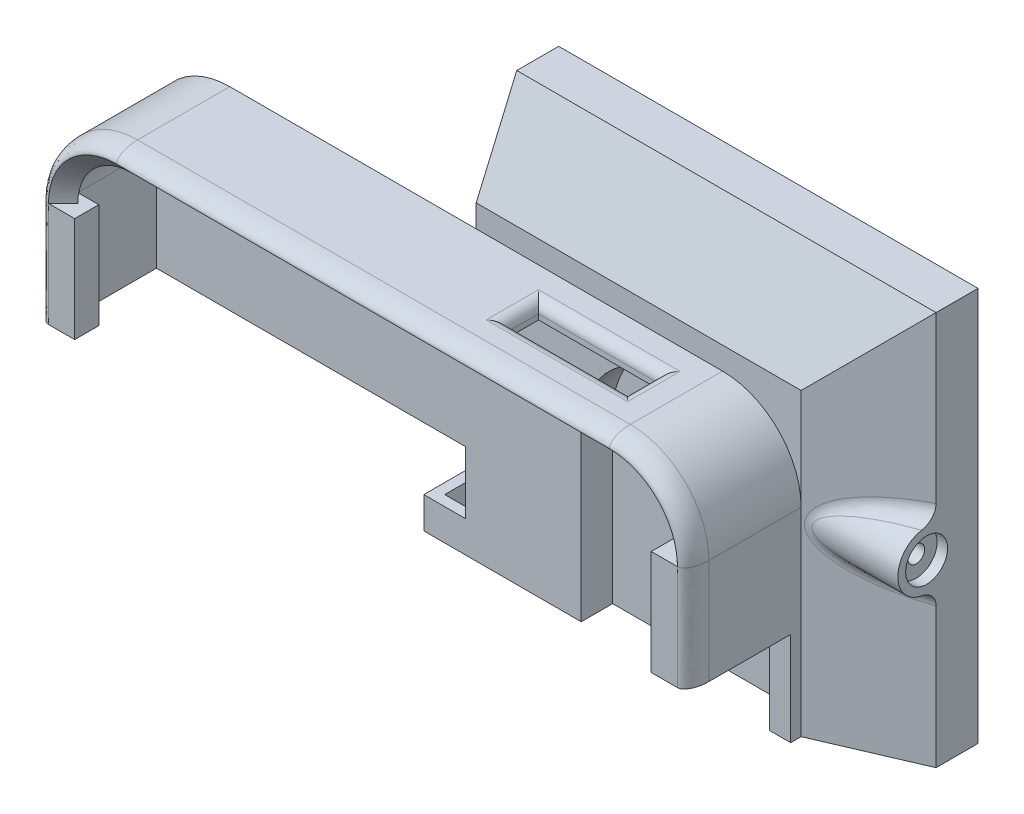
SolidWorks part; units mm, degrees
ref_plane "Front Plane" through (0, 0, 0) normal (0, 0, 1) x (1, 0, 0)
ref_plane "Top Plane" through (0, 0, 0) normal (0, 1, 0) x (1, 0, 0)
ref_plane "Right Plane" through (0, 0, 0) normal (1, 0, 0) x (0, 0, -1)
sketch "Sketch1" plane through (0, 0, 0) normal (0, 0, 1) x (1, 0, 0)
  line L0 (31, 17.5) -> (31, 0)
  line L1 (0, 0) -> (62, 0)
  line L2 (0, 0) -> (0, 10)
  line L3 (7.5, 17.5) -> (54.5, 17.5)
  line L4 (62, 0) -> (62, 10)
  line L5 (7.5, 16) -> (54.5, 16)
  line L9 (1.5, 0) -> (1.5, 10)
  line L12 (60.5, 10) -> (60.5, 0)
  arc A0 (0, 10) -> (7.5, 17.5) centre (7.5, 10) cw
  arc A1 (62, 10) -> (54.5, 17.5) centre (54.5, 10) ccw
  arc A2 (1.5, 10) -> (7.5, 16) centre (7.5, 10) cw
  arc A3 (60.5, 10) -> (54.5, 16) centre (54.5, 10) ccw
  dimension "D5" = 1.5
extrude "Boss-Extrude1" add sketch "Sketch1" along normal blind 10.8 contours L9 A2 L5 L0 L3 A0 L2 L1 | A3 L12 L1 L4 A1 L3 L0 L5 region at (42.75, 17.144, 0) region at (30.644, 16.75, 0)
sketch "Sketch2" plane through (0, 0, 0) normal (0, 0, -1) x (-1, 0, 0)
  line L0 (-1.5, 0) -> (-1.5, 10)
  line L1 (-7.5, 16) -> (-54.5, 16)
  line L2 (-60.5, 0) -> (-60.5, 10)
  line L3 (-60.5, 0) -> (-1.5, 0)
  arc A0 (-1.5, 10) -> (-7.5, 16) centre (-7.5, 10) ccw
  arc A1 (-54.5, 16) -> (-60.5, 10) centre (-54.5, 10) ccw
extrude "Boss-Extrude2" add sketch "Sketch2" against normal blind 1 separate body
combine bodies "Combine1" operation type add bodies to combine 102 101
sketch "Sketch3" plane through (0, 0, 10.8) normal (0, 0, 1) x (1, 0, 0)
  line L0 (0, 0) -> (3.5, 0)
  line L1 (0, 0) -> (0, 10)
  line L2 (0, 0) -> (0, 10) construction
  line L3 (3.5, 0) -> (3.5, 10)
  line L4 (3.5, 10) -> (0, 10)
  line L5 (1.5, 10) -> (1.5, 0)
  line L6 (31, 16) -> (31, -7.5027)
  line L7 (7.5, 16) -> (54.5, 16) construction
  line L8 (60.5, 10) -> (60.5, 0)
  line L9 (62, 0) -> (58.5, 0)
  line L10 (58.5, 10) -> (62, 10)
  line L11 (58.5, 0) -> (58.5, 10)
  line M7 (1.5, 0) -> (1.5, 10)
  line M11 (60.5, 10) -> (60.5, 0)
  dimension "D1" = 3.5
  dimension "D2" = 10
extrude "Boss-Extrude3" add sketch "Sketch3" against normal blind 2.3 contours L3 L4 L0 M7 | L11 L9 L10 M11 region at (2.5, 5, 10.8) region at (59.5, 5, 10.8)
fillet "Fillet1" radius 1 5 edges at (0, 5, 10.8) (62, 5, 10.8) (2.1967, 15.3033, 10.8) (59.8033, 15.3033, 10.8) (31, 17.5, 10.8) second distance 2 first distance on face at (31, 9.4708, 10.8)
sketch "Sketch4" plane through (0, 17.5, 0) normal (0, 1, 0) x (1, 0, 0)
  line L0 (62, -8.8) -> (62, 0) construction
  line L1 (51.5, -6.05) -> (40, -6.05)
  line L2 (51.5, -6.05) -> (51.5, -3.05)
  line L3 (51.5, -3.05) -> (40, -3.05)
  line L4 (40, -6.05) -> (40, -3.05)
  line L5 (7.5, 0) -> (54.5, 0) construction
  dimension "D1" = 10.5
  dimension "D2" = 11.5
  dimension "D3" = 3.05
  dimension "D4" = 3
extrude "Cut-Extrude1" cut sketch "Sketch4" against normal up to next
sketch "Sketch5" plane through (0, 0, 10.8) normal (0, 0, 1) x (1, 0, 0)
  line L1 (7.5, 15) -> (54.5, 15)
  line L2 (7.5, 16) -> (54.5, 16) construction
  line L4 (3.5, 10) -> (1.5, 10) construction
  line L5 (31, 16.5) -> (31, -2.3238) construction
  line L6 (54.5, 16.5) -> (7.5, 16.5) construction
  line L7 (59.5, 10) -> (60.5, 10)
  line L8 (54.5, 16) -> (7.5, 16)
  line L9 (1.5, 10) -> (2.5, 10)
  arc A1 (2.5, 10) -> (7.5, 15) centre (7.5, 10) cw
  arc A2 (59.5, 10) -> (54.5, 15) centre (54.5, 10) ccw
  arc A3 (60.5, 10) -> (54.5, 16) centre (54.5, 10) ccw
  arc A4 (7.5, 16) -> (1.5, 10) centre (7.5, 10) ccw
  dimension "D1" = 1
extrude "Boss-Extrude4" add sketch "Sketch5" against normal blind 2.3
chamfer "Chamfer1" distance 1.5 angle 45 3 edges at (58.0355, 13.5355, 10.8) (31, 15, 10.8) (3.9645, 13.5355, 10.8)
chamfer "Chamfer3" distance 1 angle 45 3 edges at (58.0355, 13.5355, 8.5) (31, 15, 8.5) (3.9645, 13.5355, 8.5)
sketch "Sketch6" plane through (0, 0, 0) normal (0, 0, -1) x (-1, 0, 0)
  line L0 (-59.98, 0) -> (-59.98, 6.7)
  line L1 (-59.98, 0) -> (-42.02, 0)
  line L2 (-42.02, 0) -> (-42.02, 6.7)
  arc A0 (-42.02, 6.7) -> (-59.98, 6.7) centre (-51, 6.7) ccw
extrude "Cut-Extrude2" cut sketch "Sketch6" against normal blind 2
sketch "Sketch9" plane through (0, 0, 0) normal (0, 0, -1) x (-1, 0, 0)
  line L0 (-62, 10) -> (-62, 0)
  line L1 (-62, 0) -> (-59.98, 0)
  line L2 (-59.98, 0) -> (-59.98, 6.7)
  line L3 (-42.02, 6.7) -> (-42.02, 0)
  line L4 (-42.02, 0) -> (-40, 0)
  line L5 (-42.02, 0) -> (0, 0) construction
  line L6 (-40, 0) -> (-40, 10)
  line L8 (-54.5, 17.5) -> (-47.5, 17.5)
  arc A0 (-59.98, 6.7) -> (-42.02, 6.7) centre (-51, 6.7) cw
  arc A1 (-47.5, 17.5) -> (-40, 10) centre (-47.5, 10) cw
  arc A2 (-54.5, 17.5) -> (-62, 10) centre (-54.5, 10) ccw
extrude "Boss-Extrude6" add sketch "Sketch9" along normal blind 2
fillet "Fillet2" radius 1 4 edges at (45.75, 17.5, 3.05) (51.5, 17.5, 4.55) (45.75, 17.5, 6.05) (40, 17.5, 4.55)
sketch "Sketch10" plane through (0, 0, -2) normal (0, 0, -1) x (-1, 0, 0)
  line L0 (-62, 10) -> (-62, 0)
  line L1 (-62, 0) -> (-40, 0)
  line L2 (-40, 0) -> (-40, 10)
  line L3 (-54.5, 17.5) -> (-47.5, 17.5)
  arc A0 (-62, 10) -> (-54.5, 17.5) centre (-54.5, 10) cw
  arc A1 (-40, 10) -> (-47.5, 17.5) centre (-47.5, 10) ccw
extrude "Boss-Extrude7" add sketch "Sketch10" along normal blind 1.87
sketch "Sketch11" plane through (0, 0, -2) normal (0, 0, 1) x (1, 0, 0)
  circle A0 centre (51, 8.65) radius 2.5
  dimension "D1" = 5
extrude "Cut-Extrude3" cut sketch "Sketch11" against normal through all
sketch "Sketch20" plane through (0, 0, -3.87) normal (0, 0, -1) x (-1, 0, 0)
  line L0 (-51, 28.65) -> (-51, -11.35) construction
  line L1 (-71, 28.65) -> (-31, 28.65)
  line L2 (-71, 28.65) -> (-71, -11.35)
  line L3 (-71, -11.35) -> (-31, -11.35)
  line L4 (-31, 28.65) -> (-31, -11.35)
  line L5 (-71, 8.65) -> (-31, 8.65) construction
  line L7 (-68.6, 26.25) -> (-33.4, 26.25)
  line L8 (-68.6, 26.25) -> (-68.6, -8.95)
  line L9 (-68.6, -8.95) -> (-33.4, -8.95)
  line L10 (-33.4, 26.25) -> (-33.4, -8.95)
  circle A0 centre (-51, 8.65) radius 2.5 construction
  dimension "D1" = 40
  dimension "D2" = 40
  dimension "D3" = 0
  dimension "D4" = 0
  dimension "D5" = 35.2
  dimension "D6" = 35.2
  dimension "D7" = 17.6
  dimension "D8" = 17.6
extrude "Boss-Extrude8" add sketch "Sketch20" along normal blind 4 separate body
sketch "Sketch21" plane through (0, 0, 0) normal (0, -1, 0) x (1, 0, 0)
  line L0 (62, -3.87) -> (71, -3.87)
  line L1 (71, -3.87) -> (62, 0)
  line L2 (62, 8.8) -> (62, -3.87) construction
  line L3 (62, 0) -> (62, -3.87)
  dimension "D1" = 9
extrude "Boss-Extrude9" add sketch "Sketch21" along normal up to surface and the other way up to surface up to face at (51, -11.35, -5.87) other way up to face at (51, 28.65, -5.87)
sketch "Sketch28" plane through (0, 0, 0) normal (0, 0, -1) x (-1, 0, 0)
  line L0 (-31, 17.5) -> (-31, 0)
  line L1 (-31, -11.35) -> (-31, 28.65) construction
  line L4 (-40, 10) -> (-40, 0)
  line L5 (-40, 0) -> (0, 0)
  line L6 (0, 0) -> (0, 10)
  line L7 (-7.5, 17.5) -> (-47.5, 17.5)
  line L8 (-40, 10) -> (-40, 0)
  line L9 (-40, 0) -> (0, 0)
  line L10 (0, 0) -> (0, 10)
  line L11 (-7.5, 17.5) -> (-47.5, 17.5)
  arc A2 (-40, 10) -> (-47.5, 17.5) centre (-47.5, 10) ccw
  arc A3 (0, 10) -> (-7.5, 17.5) centre (-7.5, 10) ccw
  arc A4 (-40, 10) -> (-47.5, 17.5) centre (-47.5, 10) ccw
  arc A5 (0, 10) -> (-7.5, 17.5) centre (-7.5, 10) ccw
  arc M7 (-47.5, 17.5) -> (-40, 10) centre (-47.5, 10) cw
  line M8 (-40, 10) -> (-40, 0)
  line M9 (-40, 0) -> (0, 0)
  line M12 (-7.5, 17.5) -> (-47.5, 17.5)
  dimension "D1" = 0
extrude "Boss-Extrude22" add sketch "Sketch28" along normal up to surface (3.87 mm away) contours L0 M12 M7 M8 M9 region at (35.9396, 9.2536, 0) up to face at (53.5, 8.65, -3.87)
sketch "Sketch29" plane through (31, 0, 0) normal (-1, 0, 0) x (0, 0, 1)
  line L0 (-3.87, 28.65) -> (-3.87, 19.65)
  line L1 (-3.87, 17.5) -> (-3.87, 28.65) construction
  line L2 (-3.87, 19.65) -> (0, 19.65)
  line L3 (0, 19.65) -> (-3.87, 28.65)
  line L4 (-3.87, 28.65) -> (-3.8304, 28.713)
  line M6 (-3.87, 17.5) -> (-3.87, 28.65)
  dimension "D1" = 9
extrude "Boss-Extrude23" add sketch "Sketch29" against normal up to surface (40 mm away) contours L2 L3 M6 region at (31, 22.65, -2.58) up to face at (71, 8.65, -5.87)
sketch "Sketch30" plane through (0, 19.65, 0) normal (0, -1, 0) x (1, 0, 0)
  line L3 (62, 0) -> (71, -3.87)
  line L4 (71, -3.87) -> (71, 0)
  line L5 (71, 0) -> (62, 0)
  line L6 (62, 0) -> (71, -3.87)
  line L7 (71, -3.87) -> (71, 0)
  line L8 (71, 0) -> (62, 0)
  dimension "D1" = 0
extrude "Cut-Extrude8" cut sketch "Sketch30" against normal up to next
sketch "Sketch31" plane through (62, 0, 0) normal (-1, 0, 0) x (0, 0, 1)
  line L3 (0, 28.65) -> (-3.87, 28.65)
  line L4 (-3.87, 28.65) -> (0, 19.65)
  line L5 (0, 19.65) -> (0, 28.65)
  line L6 (0, 28.65) -> (-3.87, 28.65)
  line L7 (-3.87, 28.65) -> (0, 19.65)
  line L8 (0, 19.65) -> (0, 28.65)
  dimension "D1" = 0
extrude "Cut-Extrude9" cut sketch "Sketch31" against normal up to next
sketch "Sketch32" plane through (0, 19.65, 0) normal (0, -1, 0) x (1, 0, 0)
  line L5 (62, -3.87) -> (62, 0)
  line L6 (62, 0) -> (31, 0)
  line L7 (31, 0) -> (31, -3.87)
  line L8 (31, -3.87) -> (33.4, -3.87)
  line L9 (33.4, -3.87) -> (62, -3.87)
  line L10 (62, -3.87) -> (62, 0)
  line L11 (62, 0) -> (31, 0)
  line L12 (31, 0) -> (31, -3.87)
  line L13 (31, -3.87) -> (33.4, -3.87)
  line L14 (33.4, -3.87) -> (62, -3.87)
  dimension "D1" = 0
extrude "Boss-Extrude24" add sketch "Sketch32" along normal up to surface (2.15 mm away) up to face at (45.75, 17.5, 4.55)
sketch "Sketch33" plane through (0, 0, -3.87) normal (0, 0, -1) x (-1, 0, 0)
  line L0 (-54.5, 17.5) -> (-62, 17.5)
  line L1 (-62, 17.5) -> (-62, 10)
  arc A0 (-62, 10) -> (-54.5, 17.5) centre (-54.5, 10) cw
extrude "Boss-Extrude25" add sketch "Sketch33" against normal up to surface (3.87 mm away) up to face at (48.1, 18.36, 0)
sketch "Sketch34" plane through (0, 0, 0) normal (0, -1, 0) x (1, 0, 0)
  line L0 (60.5, 1) -> (62, 1)
  line L1 (31, 0) -> (31, 1)
  line L20 (0, 0) -> (31, 0)
  line L21 (31, 0) -> (31, -3.87)
  line L22 (31, -3.87) -> (33.4, -3.87)
  line L23 (33.4, -3.87) -> (62, -3.87)
  line L24 (62, -3.87) -> (62, 0)
  line L25 (62, 0) -> (62, 8.8)
  line L26 (61, 10.8) -> (58.5, 10.8)
  line L27 (58.5, 10.8) -> (58.5, 8.5)
  line L28 (58.5, 8.5) -> (60.5, 8.5)
  line L29 (60.5, 8.5) -> (60.5, 1)
  line L30 (60.5, 1) -> (59.98, 1)
  line L31 (59.98, 1) -> (59.98, -2)
  line L32 (59.98, -2) -> (42.02, -2)
  line L33 (42.02, -2) -> (42.02, 1)
  line L34 (42.02, 1) -> (1.5, 1)
  line L35 (1.5, 1) -> (1.5, 8.5)
  line L36 (1.5, 8.5) -> (3.5, 8.5)
  line L37 (3.5, 8.5) -> (3.5, 10.8)
  line L38 (3.5, 10.8) -> (1, 10.8)
  line L39 (0, 8.8) -> (0, 0)
  line L40 (0, 0) -> (31, 0)
  line L41 (31, 0) -> (31, -3.87)
  line L42 (31, -3.87) -> (33.4, -3.87)
  line L43 (33.4, -3.87) -> (62, -3.87)
  line L44 (62, -3.87) -> (62, 0)
  line L45 (62, 0) -> (62, 8.8)
  line L46 (61, 10.8) -> (58.5, 10.8)
  line L47 (58.5, 10.8) -> (58.5, 8.5)
  line L48 (58.5, 8.5) -> (60.5, 8.5)
  line L49 (60.5, 8.5) -> (60.5, 1)
  line L50 (60.5, 1) -> (59.98, 1)
  line L51 (59.98, 1) -> (59.98, -2)
  line L52 (59.98, -2) -> (42.02, -2)
  line L53 (42.02, -2) -> (42.02, 1)
  line L54 (42.02, 1) -> (1.5, 1)
  line L55 (1.5, 1) -> (1.5, 8.5)
  line L56 (1.5, 8.5) -> (3.5, 8.5)
  line L57 (3.5, 8.5) -> (3.5, 10.8)
  line L58 (3.5, 10.8) -> (1, 10.8)
  line L59 (0, 8.8) -> (0, 0)
  spline S2 degree 2 poles (-2769.6454, -979.1152) (73.4069, -63.5955) (61.954, 9.3993) (61.9047, 9.714) (61.807, 9.9811) (61.6887, 10.3047) (61.5165, 10.5125) (61.4097, 10.6416) (61.2894, 10.7144) (34.7566, 26.7839) (-231.209, -2974.6133) knots -62.059776 -62.059776 -62.059776 0.25 0.25 0.5 0.5 0.75 0.75 0.875 0.875 24.347049 24.347049 24.347049 only from (62, 8.8) to (61, 10.8)
  spline S3 degree 2 poles (259.0787, -2977.8645) (27.3521, 26.7647) (0.7111, 10.7147) (0.592, 10.643) (0.4846, 10.5139) (0.3135, 10.3082) (0.1946, 9.9856) (0.0962, 9.7183) (0.0462, 9.4006) (-11.3863, -63.1555) (2809.0718, -1041.6058) knots -23.400529 -23.400529 -23.400529 0.125 0.125 0.25 0.25 0.5 0.5 0.75 0.75 62.676656 62.676656 62.676656 only from (1, 10.8) to (0, 8.8)
  spline S4 degree 2 poles (62, 8.8) (62, 9.1064) (61.954, 9.3993) (61.9047, 9.714) (61.807, 9.9811) (61.6887, 10.3047) (61.5165, 10.5125) (61.4097, 10.6416) (61.2894, 10.7144) (61.1481, 10.8) (61, 10.8) knots 0 0 0 0.25 0.25 0.5 0.5 0.75 0.75 0.875 0.875 1 1 1
  spline S5 degree 2 poles (1, 10.8) (0.8527, 10.8) (0.7111, 10.7147) (0.592, 10.643) (0.4846, 10.5139) (0.3135, 10.3082) (0.1946, 9.9856) (0.0962, 9.7183) (0.0462, 9.4006) (0, 9.1077) (0, 8.8) knots 0 0 0 0.125 0.125 0.25 0.25 0.5 0.5 0.75 0.75 1 1 1
  line M24 (31, 0) -> (31, -3.87)
  line M25 (31, -3.87) -> (33.4, -3.87)
  line M26 (33.4, -3.87) -> (62, -3.87)
  line M27 (62, -3.87) -> (62, 0)
  line M28 (62, 0) -> (62, 8.8)
  line M34 (60.5, 1) -> (59.98, 1)
  line M35 (59.98, 1) -> (59.98, -2)
  line M36 (59.98, -2) -> (42.02, -2)
  line M37 (42.02, -2) -> (42.02, 1)
  line M38 (42.02, 1) -> (1.5, 1)
  dimension "D1" = 0
extrude "Boss-Extrude26" add sketch "Sketch34" along normal up to surface (11.35 mm away) contours L1 L0 M24 M25 M26 M27 M28 M34 M35 M36 M37 M38 region at (58.1075, 0, -2.3535) region at (39.3369, 0, -1.8217) up to face at (57.25, -11.35, -4.8808)
sketch "Sketch37" plane through (71, 0, 0) normal (1, 0, 0) x (0, 0, -1)
  line L1 (3.87, -11.35) -> (3.87, 28.65) construction
  circle A0 centre (2.97, 8.65) radius 0.8065
  dimension "D2" = 1.613
  dimension "D3" = 0.9
  dimension "D1" = 17.6
extrude "Cut-Extrude13" cut sketch "Sketch37" against normal up to surface (17.5 mm away) up to face at (53.5, 8.65, -2)
sketch "Sketch38" plane through (71, 0, 0) normal (1, 0, 0) x (0, 0, -1)
  line L0 (3.87, 11.2486) -> (3.87, 6.0514)
  line L1 (3.87, -11.35) -> (3.87, 28.65) construction
  circle A0 centre (2.97, 8.65) radius 2.75
  line M3 (3.87, 28.65) -> (3.87, -11.35)
  dimension "D1" = 5.5
extrude "Boss-Extrude27" add sketch "Sketch38" against normal up to surface (9 mm away) contours A0 M3 region at (71, 8.65, -2.2712) up to face at (62, 0.3833, 4.65)
sketch "Sketch39" plane through (71, 0, 0) normal (1, 0, 0) x (0, 0, -1)
  circle A0 centre (2.97, 8.65) radius 2
  dimension "D1" = 4
extrude "Cut-Extrude15" cut sketch "Sketch39" against normal blind 1
sketch "Sketch40" plane through (70, 0, 0) normal (1, 0, 0) x (0, 0, -1)
  circle A0 centre (2.97, 8.65) radius 0.8065
  dimension "D1" = 1.613
extrude "Cut-Extrude16" cut sketch "Sketch40" against normal up to surface (21.5 mm away) up to face at (53.4961, 8.79, -2.1757)
fillet "Fillet3" radius 1.5 1 edges at (62.5116, 8.65, -0.22)
sketch "Sketch41" plane through (0, -11.35, 0) normal (0, -1, 0) x (1, 0, 0)
  line L10 (71, -3.87) -> (62, 0)
  line L11 (62, 0) -> (62, 1)
  line L12 (62, 1) -> (59.98, 1)
  line L13 (59.98, 1) -> (59.98, -2)
  line L14 (59.98, -2) -> (42.02, -2)
  line L15 (42.02, -2) -> (42.02, 1)
  line L16 (42.02, 1) -> (31, 1)
  line L17 (31, 1) -> (31, -7.87)
  line L18 (31, -7.87) -> (71, -7.87)
  line L19 (71, -7.87) -> (71, -3.87)
  line L20 (71, -3.87) -> (62, 0)
  line L21 (62, 0) -> (62, 1)
  line L22 (62, 1) -> (59.98, 1)
  line L23 (59.98, 1) -> (59.98, -2)
  line L24 (59.98, -2) -> (42.02, -2)
  line L25 (42.02, -2) -> (42.02, 1)
  line L26 (42.02, 1) -> (31, 1)
  line L27 (31, 1) -> (31, -7.87)
  line L28 (31, -7.87) -> (71, -7.87)
  line L29 (71, -7.87) -> (71, -3.87)
  dimension "D1" = 0
extrude "Cut-Extrude17" cut sketch "Sketch41" against normal up to surface (2.4 mm away) up to face at (51, -8.95, -5.87)
sketch "Sketch42" plane through (0, -8.95, 0) normal (0, -1, 0) x (1, 0, 0)
  line L1 (31, 1) -> (27, 1)
  line L2 (31, 1) -> (31, -4)
  line L3 (31, -4) -> (27, -4)
  line L4 (27, 1) -> (27, -4)
  line L5 (31, -2.5) -> (28, -2.5)
  line L6 (31, -2.5) -> (31, 0)
  line L7 (31, 0) -> (28, 0)
  line L8 (28, -2.5) -> (28, 0)
  line M17 (31, 1) -> (31, -7.87)
  dimension "D1" = 5
  dimension "D2" = 4
  dimension "D3" = 1
  dimension "D4" = 1
  dimension "D5" = 1.5
extrude "Boss-Extrude28" add sketch "Sketch42" against normal blind 3 contours L5 L8 L7 L1 L4 L3 L2 M17 region at (30.936, -8.95, 0.5)
